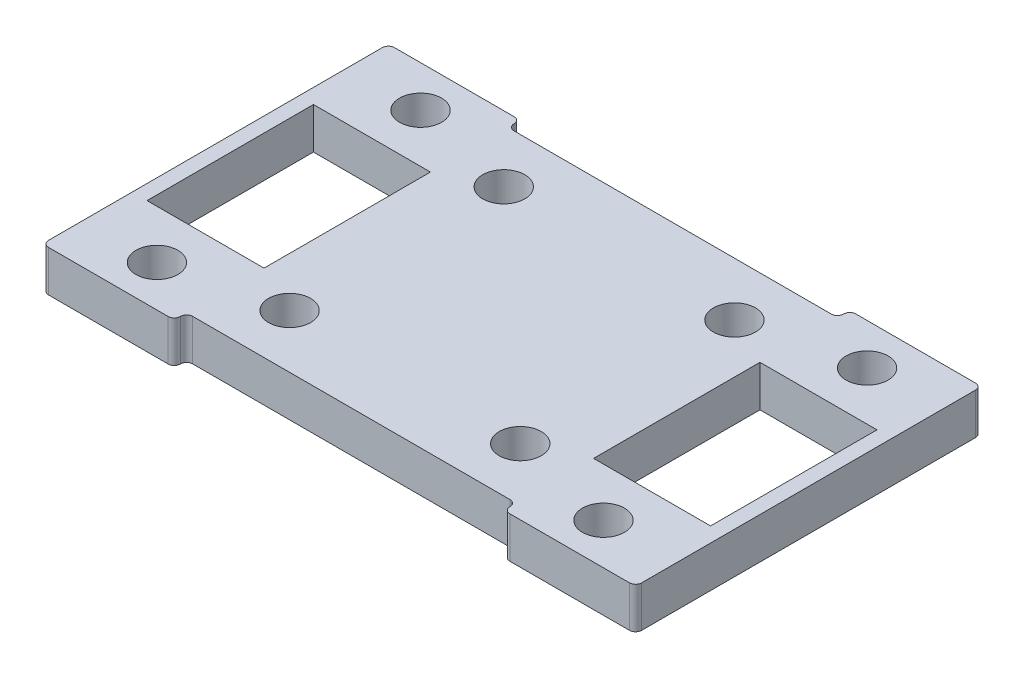
SolidWorks part; units mm, degrees
material "Alloy Steel"
ref_plane "Front Plane" through (0, 0, 0) normal (0, 0, 1) x (1, 0, 0)
ref_plane "Top Plane" through (0, 0, 0) normal (0, 1, 0) x (1, 0, 0)
ref_plane "Right Plane" through (0, 0, 0) normal (1, 0, 0) x (0, 0, -1)
sketch "Sketch1" plane through (0, 0, 0) normal (0, 1, 0) x (1, 0, 0)
  line L0 (20, 19.5) -> (20, -19.5) construction
  line L1 (-19.26, -19.5) -> (19.26, -19.5)
  line L3 (-19.26, 19.5) -> (19.26, 19.5)
  line L5 (20, 20.24) -> (20, 20.26)
  line L7 (20.74, 21) -> (35.26, 21)
  line L8 (20, 19.5) -> (-20, -19.5) construction
  line L9 (-20, 19.5) -> (20, -19.5) construction
  line L10 (0, 0) -> (0, 19.5) construction
  line L11 (0, 0) -> (-20, 0) construction
  line L12 (36, 20.26) -> (36, -20.26)
  line L13 (35.26, -21) -> (20.74, -21)
  line L14 (20, -20.26) -> (20, -20.24)
  line L16 (20, 10.1) -> (34.2, 10.1)
  line L17 (34.2, 10.1) -> (34.2, -10.1)
  line L18 (34.2, -10.1) -> (20, -10.1)
  line L19 (20, -10.1) -> (20, 10.1)
  line L20 (-20, 19.5) -> (-20, -19.5) construction
  line L21 (-20, -10.1) -> (-20, 10.1)
  line L22 (-34.2, -10.1) -> (-20, -10.1)
  line L23 (-34.2, 10.1) -> (-34.2, -10.1)
  line L24 (-20, 10.1) -> (-34.2, 10.1)
  line L25 (-20, -20.26) -> (-20, -20.24)
  line L26 (-35.26, -21) -> (-20.74, -21)
  line L27 (-36, 20.26) -> (-36, -20.26)
  line L28 (-20.74, 21) -> (-35.26, 21)
  line L29 (-20, 20.24) -> (-20, 20.26)
  circle A0 centre (-14, 13) radius 2.55
  circle A1 centre (14, 13) radius 2.55
  circle A2 centre (14, -13) radius 2.55
  circle A3 centre (-14, -13) radius 2.55
  circle A4 centre (27.1, 16) radius 2.55
  circle A5 centre (27.1, -16) radius 2.55
  circle A6 centre (-27.1, -16) radius 2.55
  circle A7 centre (-27.1, 16) radius 2.55
  arc A8 (35.26, 21) -> (36, 20.26) centre (35.26, 20.26) cw
  arc A9 (36, -20.26) -> (35.26, -21) centre (35.26, -20.26) cw
  arc A10 (-35.26, -21) -> (-36, -20.26) centre (-35.26, -20.26) cw
  arc A11 (-36, 20.26) -> (-35.26, 21) centre (-35.26, 20.26) cw
  arc A12 (-20.74, 21) -> (-20, 20.26) centre (-20.74, 20.26) cw
  arc A13 (-20, 20.24) -> (-19.26, 19.5) centre (-19.26, 20.24) ccw
  arc A14 (20, 20.26) -> (20.74, 21) centre (20.74, 20.26) cw
  arc A15 (19.26, 19.5) -> (20, 20.24) centre (19.26, 20.24) ccw
  arc A16 (19.26, -19.5) -> (20, -20.24) centre (19.26, -20.24) cw
  arc A17 (20.74, -21) -> (20, -20.26) centre (20.74, -20.26) cw
  arc A18 (-20, -20.26) -> (-20.74, -21) centre (-20.74, -20.26) cw
  arc A19 (-19.26, -19.5) -> (-20, -20.24) centre (-19.26, -20.24) ccw
  point P0 (0, 0)
  point P30 (34.2, 0)
  point P46 (27.1, 10.1)
  point P48 (36, 21)
  point P51 (36, -21)
  point P54 (-36, -21)
  point P57 (-36, 21)
  point P60 (-20, 21)
  point P66 (20, 21)
  point P75 (20, -21)
  point P78 (-20, -21)
  dimension "D5" = 5.1
  dimension "D12" = 20.2
  dimension "D13" = 0.74
  dimension "D9" = 5.1
  dimension "D1" = 1.5
  dimension "D2" = 39
  dimension "D3" = 40
  dimension "D4" = 1.5
  dimension "D6" = 14
  dimension "D7" = 6.5
  dimension "D8" = 16
  dimension "D10" = 16
  dimension "D11" = 14.2
extrude "Boss-Extrude1" add sketch "Sketch1" along normal blind 5
